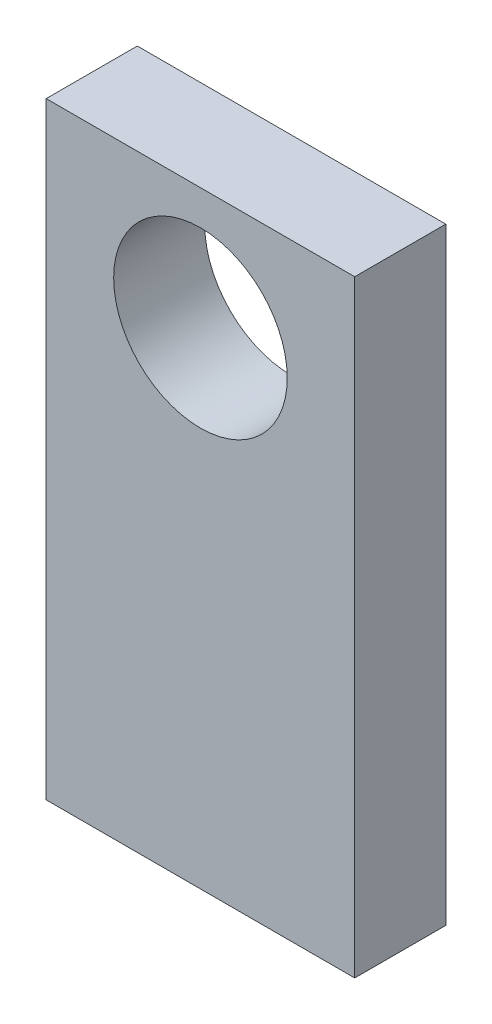
SolidWorks part; units mm, degrees
material "Cedro"
ref_plane "Alzado" through (0, 0, 0) normal (0, 0, 1) x (1, 0, 0)
ref_plane "Planta" through (0, 0, 0) normal (0, 1, 0) x (1, 0, 0)
ref_plane "Vista lateral" through (0, 0, 0) normal (1, 0, 0) x (0, 0, -1)
sketch "Croquis1" plane through (0, 0, 0) normal (0, 1, 0) x (1, 0, 0)
  line L1 (-25.4, -7.5) -> (25.4, -7.5)
  line L2 (-25.4, -7.5) -> (-25.4, 7.5)
  line L3 (-25.4, 7.5) -> (25.4, 7.5)
  line L4 (25.4, -7.5) -> (25.4, 7.5)
  line L5 (-25.4, -7.5) -> (25.4, 7.5) construction
  line L6 (-25.4, 7.5) -> (25.4, -7.5) construction
  point P0 (0, 0)
  dimension "D1" = 15
  dimension "D2" = 50.8
extrude "Saliente-Extruir1" add sketch "Croquis1" along normal blind 100
sketch "Croquis2" plane through (0, 0, 7.5) normal (0, 0, 1) x (1, 0, 0)
  line L0 (-25.4, 100) -> (25.4, 100) construction
  circle A0 centre (0, 80) radius 14.29
  dimension "D1" = 20
  dimension "D2" = 28.58
extrude "Cortar-Extruir1" cut sketch "Croquis2" against normal through all
